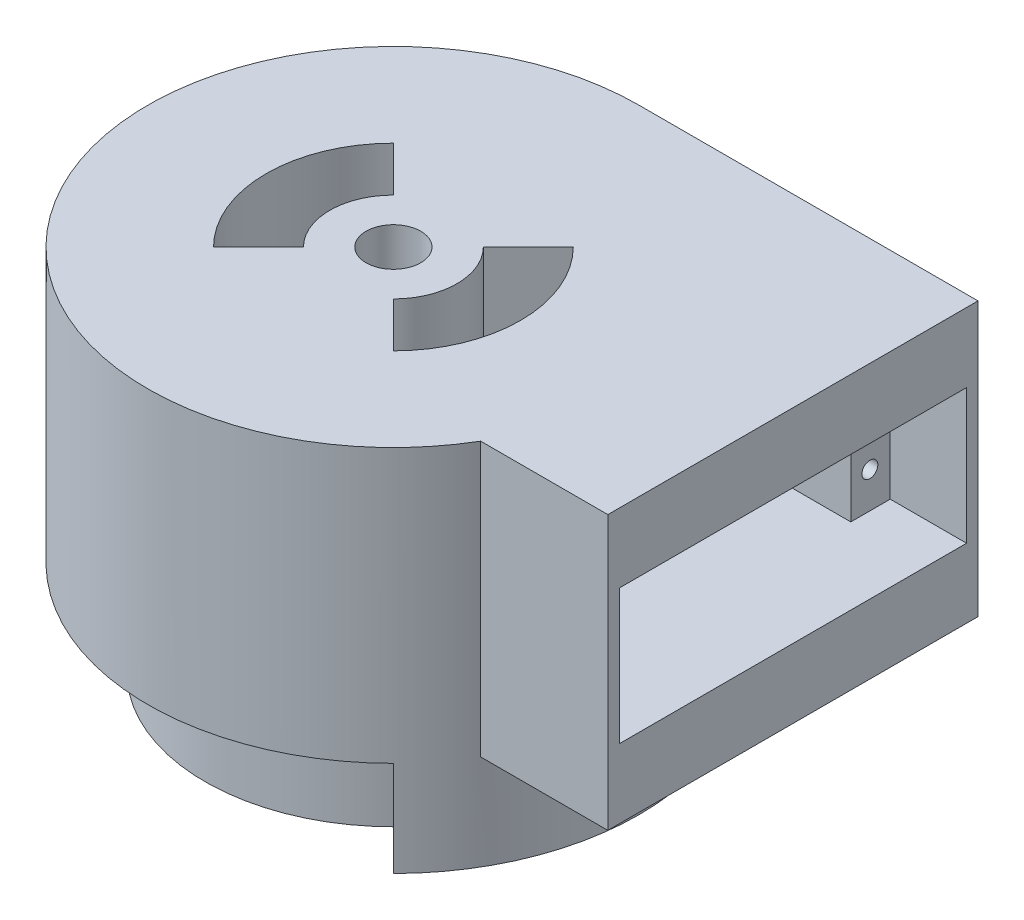
SolidWorks part; units mm, degrees
ref_plane "Front Plane" through (0, 0, 0) normal (0, 0, 1) x (1, 0, 0)
ref_plane "Top Plane" through (0, 0, 0) normal (0, 1, 0) x (1, 0, 0)
ref_plane "Right Plane" through (0, 0, 0) normal (1, 0, 0) x (0, 0, -1)
sketch "Sketch1" plane through (0, 0, 0) normal (0, 1, 0) x (1, 0, 0)
  line L0 (0, 38.625) -> (53.2973, 38.625)
  line L1 (53.2973, 38.625) -> (53.2973, -19.575)
  line L2 (53.2973, -19.575) -> (33.2973, -19.575)
  line L3 (0, 60.3307) -> (0, -56.6529) construction
  arc A0 (0, 38.625) -> (33.2973, -19.575) centre (0, 0) ccw
  dimension "D1" = 20
  dimension "D2" = 38.625
  dimension "D7" = 58.2
extrude "Boss-Extrude1" add sketch "Sketch1" along normal blind 43
sketch "Sketch4" plane through (0, 0, 0) normal (0, -1, 0) x (1, 0, 0)
  line L0 (-38.625, 0) -> (53.2973, 0) construction
  line L1 (53.2973, 19.575) -> (53.2973, -38.625) construction
  line L2 (20.948, 20.948) -> (27.312, 27.312)
  line L3 (20.948, -20.948) -> (27.312, -27.312)
  line L4 (20.948, -20.948) -> (0, 0) construction
  line L5 (0, 0) -> (20.948, 20.948) construction
  arc A0 (33.2973, 19.575) -> (0, -38.625) centre (0, 0) ccw construction
  arc A1 (20.948, 20.948) -> (20.948, -20.948) centre (0, 0) ccw
  arc A4 (27.312, -27.312) -> (27.312, 27.312) centre (0, 0) ccw
  dimension "D1" = 45
  dimension "D2" = 45
  dimension "D3" = 9
extrude "Boss-Extrude2" add sketch "Sketch4" along normal blind 15
sketch "Sketch5" plane through (53.2973, 0, 0) normal (1, 0, 0) x (0, 0, -1)
  line L0 (9.525, 43) -> (9.525, 0) construction
  line L1 (-19.575, 43) -> (38.625, 43) construction
  line L2 (-19.575, 0) -> (38.625, 0) construction
  line L3 (-19.575, 21.5) -> (38.625, 21.5) construction
  line L4 (-19.575, 43) -> (-19.575, 0) construction
  line L5 (38.625, 43) -> (38.625, 0) construction
  line L6 (-14.575, 26.45) -> (-14.575, 16.55) construction
  line L7 (-10.975, 11.5) -> (30.025, 11.5) construction
  line L8 (-10.975, 11.5) -> (-10.975, 31.5) construction
  line L9 (-10.975, 31.5) -> (30.025, 31.5) construction
  line L10 (30.025, 11.5) -> (30.025, 31.5) construction
  line L11 (-10.975, 11.5) -> (30.025, 31.5) construction
  line L12 (-10.975, 31.5) -> (30.025, 11.5) construction
  line L13 (33.625, 26.45) -> (33.625, 16.55) construction
  line L14 (-11.575, 10.9) -> (-11.575, 32.1)
  line L15 (-11.575, 32.1) -> (30.625, 32.1)
  line L16 (30.625, 32.1) -> (30.625, 10.9)
  line L17 (30.625, 10.9) -> (-11.575, 10.9)
  line L18 (-11.575, 10.9) -> (-17.775, 10.9)
  line L19 (-17.775, 10.9) -> (-17.775, 32.1)
  line L20 (-17.775, 32.1) -> (-11.575, 32.1)
  line L21 (30.625, 32.1) -> (36.825, 32.1)
  line L22 (36.825, 32.1) -> (36.825, 10.9)
  line L23 (36.825, 10.9) -> (30.625, 10.9)
  circle A0 centre (-14.575, 26.45) radius 1.25
  circle A1 centre (-14.575, 16.55) radius 1.25
  circle A2 centre (33.625, 16.55) radius 1.25
  circle A3 centre (33.625, 26.45) radius 1.25
  circle A4 centre (19.625, 21.5) radius 6 construction
  point P12 (9.525, 21.5)
  point P25 (-14.575, 21.5)
  point P27 (33.625, 21.5)
  point P38 (9.525, 32.1)
  point P39 (-17.775, 21.5)
  dimension "D8" = 2.5
  dimension "D9" = 2.5
  dimension "D10" = 2.5
  dimension "D11" = 2.5
  dimension "D14" = 12
  dimension "D13" = 17.2
  dimension "D1" = 9.9
  dimension "D2" = 9.9
  dimension "D3" = 24.1
  dimension "D4" = 24.1
  dimension "D5" = 0.6
  dimension "D6" = 20
  dimension "D7" = 54.6
  dimension "D12" = 0.6
  dimension "D15" = 41
extrude "Cut-Extrude1" cut sketch "Sketch5" against normal blind 41 contours L17 L16 L15 L14 region at (53.2973, 21.5, -9.525)
extrude "Cut-Extrude2" cut sketch "Sketch5<5>" against normal blind 12 contours L20 L19 L18 L14 A1 A0 | L23 L22 L21 L16 A3 A2 region at (53.2973, 21.5, 14.6831) region at (53.2973, 21.5, -33.7331)
sketch "Sketch5<5>" plane through (53.2973, 0, 0) normal (1, 0, 0) x (0, 0, -1) same geometry as "Sketch5"
extrude "Cut-Extrude3" cut sketch "Sketch5<6>" against normal blind 35 contours A3 | A2 | A0 | A1 region at (53.2973, 26.45, 14.575) region at (53.2973, 16.55, 14.575) region at (53.2973, 16.55, -33.625) region at (53.2973, 26.45, -33.625)
sketch "Sketch5<6>" plane through (53.2973, 0, 0) normal (1, 0, 0) x (0, 0, -1) same geometry as "Sketch5"
sketch "Sketch6" plane through (0, -15, 0) normal (0, -1, 0) x (1, 0, 0)
  line L0 (0, -38.625) -> (0, 38.625) construction
  line L1 (38.625, 0) -> (-38.625, 0) construction
  line L2 (7.0711, 7.0711) -> (14.1421, 14.1421)
  line L3 (7.0711, -7.0711) -> (14.1421, -14.1421)
  line L4 (0, 0) -> (7.0711, 7.0711) construction
  line L5 (7.0711, -7.0711) -> (0, 0) construction
  line L6 (-7.0711, -7.0711) -> (-14.1421, -14.1421)
  line L7 (-7.0711, 7.0711) -> (-14.1421, 14.1421)
  circle A0 centre (0, 0) radius 4.3
  arc A1 (27.312, 27.312) -> (0, -38.625) centre (0, 0) ccw construction
  arc A2 (27.312, -27.312) -> (27.312, 27.312) centre (0, 0) ccw construction
  arc A3 (7.0711, 7.0711) -> (7.0711, -7.0711) centre (0, 0) cw
  arc A4 (14.1421, -14.1421) -> (14.1421, 14.1421) centre (0, 0) ccw
  arc A5 (-14.1421, -14.1421) -> (-14.1421, 14.1421) centre (0, 0) cw
  arc A6 (-7.0711, 7.0711) -> (-7.0711, -7.0711) centre (0, 0) ccw
  dimension "D1" = 8.6
  dimension "D3" = 10
  dimension "D4" = 10
  dimension "D2" = 45
  dimension "D5" = 45
extrude "Cut-Extrude4" cut sketch "Sketch6" against normal through all both and the other way through all
sketch "Sketch7" plane through (41.2973, 0, 0) normal (1, 0, 0) x (0, 0, -1)
  line L0 (30.625, 32.1) -> (30.625, 10.9) construction
  line L1 (25.625, 18.1) -> (35.625, 18.1)
  line L2 (25.625, 18.1) -> (25.625, 24.9)
  line L3 (25.625, 24.9) -> (35.625, 24.9)
  line L4 (35.625, 18.1) -> (35.625, 24.9)
  line L5 (25.625, 18.1) -> (35.625, 24.9) construction
  line L6 (25.625, 24.9) -> (35.625, 18.1) construction
  point P0 (30.625, 21.5)
  dimension "D1" = 6.8
  dimension "D2" = 10
extrude "Cut-Extrude5" cut sketch "Sketch7" against normal through all from offset 5 offset against normal yes
